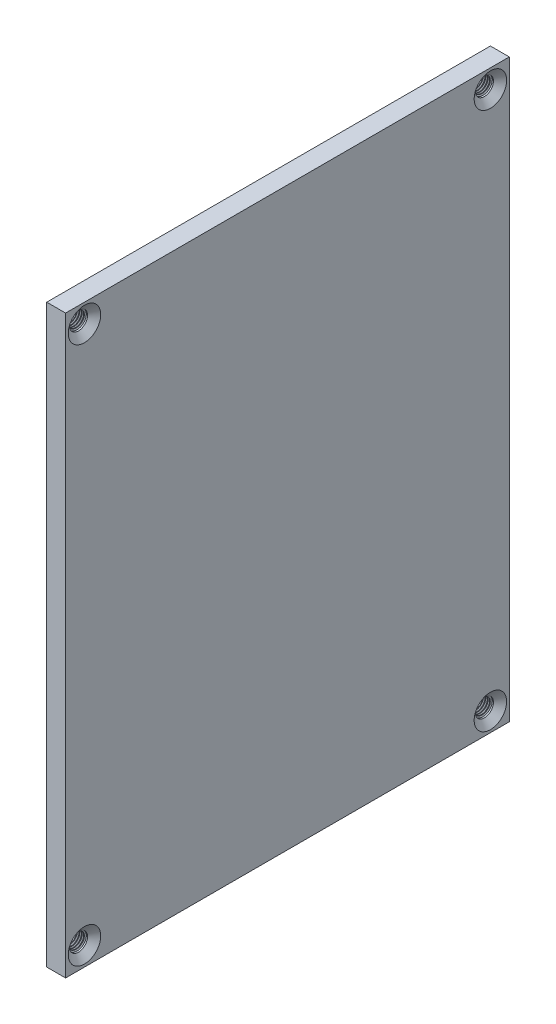
SolidWorks part; units mm, degrees
ref_plane "Front Plane" through (0, 0, 0) normal (0, 0, 1) x (1, 0, 0)
ref_plane "Top Plane" through (0, 0, 0) normal (0, 1, 0) x (1, 0, 0)
ref_plane "Right Plane" through (0, 0, 0) normal (1, 0, 0) x (0, 0, -1)
sketch "Sketch3" plane through (0, 0, 0) normal (1, 0, 0) x (0, 0, -1)
  line L1 (0, 0) -> (59.69, 0)
  line L2 (0, 0) -> (0, 77.47)
  line L3 (0, 77.47) -> (59.69, 77.47)
  line L4 (59.69, 0) -> (59.69, 77.47)
  dimension "D1" = 77.47
  dimension "D2" = 59.69
extrude "Boss-Extrude2" add sketch "Sketch3" along normal blind 2.54
sketch "Sketch6" plane through (2.54, 0, 0) normal (1, 0, 0) x (0, 0, -1)
  line L1 (0, 77.47) -> (2.54, 77.47)
  line L2 (0, 77.47) -> (0, 74.93)
  line L3 (0, 74.93) -> (2.54, 74.93)
  line L4 (2.54, 77.47) -> (2.54, 74.93)
  line L5 (59.69, 77.47) -> (57.15, 77.47)
  line L6 (59.69, 77.47) -> (59.69, 74.93)
  line L7 (59.69, 74.93) -> (57.15, 74.93)
  line L8 (57.15, 77.47) -> (57.15, 74.93)
  line L9 (0, 0) -> (2.54, 0)
  line L10 (0, 0) -> (0, 2.54)
  line L11 (0, 2.54) -> (2.54, 2.54)
  line L12 (2.54, 0) -> (2.54, 2.54)
  line L13 (59.69, 0) -> (57.15, 0)
  line L14 (59.69, 0) -> (59.69, 2.54)
  line L15 (59.69, 2.54) -> (57.15, 2.54)
  line L16 (57.15, 0) -> (57.15, 2.54)
hole_wizard "CSK for #2 Flat Head Machine Screw (100)1" positions "Sketch7" profile "Sketch9" countersink size "#2" standard "ANSI Inch" end condition through all
sketch "Sketch7" plane through (2.54, 0, 0) normal (1, 0, 0) x (0, 0, -1)
  point P0 (2.54, 74.93)
  point P3 (57.15, 74.93)
  point P6 (57.15, 2.54)
  point P9 (2.54, 2.54)
sketch "Sketch9" plane through (2.54, 74.93, -2.54) normal (0, 1, 0) x (0, 0, -1)
  line L0 (0, 0) -> (0, 2.54)
  line L1 (0, 2.54) -> (1.2192, 2.54)
  line L2 (1.2192, 2.54) -> (1.2192, 0.8099)
  line L3 (1.2192, 0.8099) -> (2.1844, 0)
  line L5 (2.1844, 0) -> (0, 0)
  line L6 (-1.2192, 0.8099) -> (-2.1844, 0) construction
  line L11 (0, -6.35) -> (0, 107.95) construction
  dimension "Thru Hole Dia." = 2.4384
  dimension "Thru Hole Depth" = 2.54
  dimension "Near C'Sink Dia." = 4.3688
  dimension "Near C'Sink Angle" = 100
thread "Thread1" pitch 0.3175 method extrude profile "Thread Profile1" start angle 0, offset 0, length 1.4478, pitch 0.3175, diameter 2.4384
ref_plane "Plane1" through (1.7301, 74.93, -1.3208) normal (0, -1, 0) x (0, 0, 1)
sketch "Thread Profile1" plane through (1.7301, 74.93, -1.3208) normal (0, -1, 0) x (0, 0, 1)
  line L0 (0, 0) -> (0, 0.3175) construction
  line L11 (0, 0) -> (0, 0.2778)
  line L12 (0, 0.2778) -> (-0.1719, 0.1786)
  line L13 (-0.1719, 0.1786) -> (-0.1719, 0.0992)
  line L15 (-0.1719, 0.0992) -> (0, 0)
  line L17 (-0.1719, 0.1389) -> (0, 0.1389) construction
  point P2 (0, 0)
  dimension "Pitch" = 0.3175
  dimension "Profile_Angle" = 60
  dimension "Profile_Land" = 0.0794
  dimension "Profile_Height" = 0.1719
thread "Thread2" pitch 0.3175 method extrude profile "Thread Profile2" start angle 0, offset 0, length 1.4478, pitch 0.3175, diameter 2.4384
ref_plane "Plane2" through (1.7301, 74.93, -55.9308) normal (0, -1, 0) x (0, 0, 1)
sketch "Thread Profile2" plane through (1.7301, 74.93, -55.9308) normal (0, -1, 0) x (0, 0, 1)
  line L0 (0, 0) -> (0, 0.3175) construction
  line L11 (0, 0) -> (0, 0.2778)
  line L12 (0, 0.2778) -> (-0.1719, 0.1786)
  line L13 (-0.1719, 0.1786) -> (-0.1719, 0.0992)
  line L15 (-0.1719, 0.0992) -> (0, 0)
  line L17 (-0.1719, 0.1389) -> (0, 0.1389) construction
  point P2 (0, 0)
  dimension "Pitch" = 0.3175
  dimension "Profile_Angle" = 60
  dimension "Profile_Land" = 0.0794
  dimension "Profile_Height" = 0.1719
thread "Thread3" pitch 0.3175 method extrude profile "Thread Profile3" start angle 0, offset 0, length 1.4478, pitch 0.3175, diameter 2.4384
ref_plane "Plane3" through (1.7301, 2.54, -55.9308) normal (0, -1, 0) x (0, 0, 1)
sketch "Thread Profile3" plane through (1.7301, 2.54, -55.9308) normal (0, -1, 0) x (0, 0, 1)
  line L0 (0, 0) -> (0, 0.3175) construction
  line L11 (0, 0) -> (0, 0.2778)
  line L12 (0, 0.2778) -> (-0.1719, 0.1786)
  line L13 (-0.1719, 0.1786) -> (-0.1719, 0.0992)
  line L15 (-0.1719, 0.0992) -> (0, 0)
  line L17 (-0.1719, 0.1389) -> (0, 0.1389) construction
  point P2 (0, 0)
  dimension "Pitch" = 0.3175
  dimension "Profile_Angle" = 60
  dimension "Profile_Land" = 0.0794
  dimension "Profile_Height" = 0.1719
thread "Thread4" pitch 0.3175 method extrude profile "Thread Profile4" start angle 0, offset 0, length 1.4478, pitch 0.3175, diameter 2.4384
ref_plane "Plane4" through (1.7301, 2.54, -1.3208) normal (0, -1, 0) x (0, 0, 1)
sketch "Thread Profile4" plane through (1.7301, 2.54, -1.3208) normal (0, -1, 0) x (0, 0, 1)
  line L0 (0, 0) -> (0, 0.3175) construction
  line L11 (0, 0) -> (0, 0.2778)
  line L12 (0, 0.2778) -> (-0.1719, 0.1786)
  line L13 (-0.1719, 0.1786) -> (-0.1719, 0.0992)
  line L15 (-0.1719, 0.0992) -> (0, 0)
  line L17 (-0.1719, 0.1389) -> (0, 0.1389) construction
  point P2 (0, 0)
  dimension "Pitch" = 0.3175
  dimension "Profile_Angle" = 60
  dimension "Profile_Land" = 0.0794
  dimension "Profile_Height" = 0.1719
